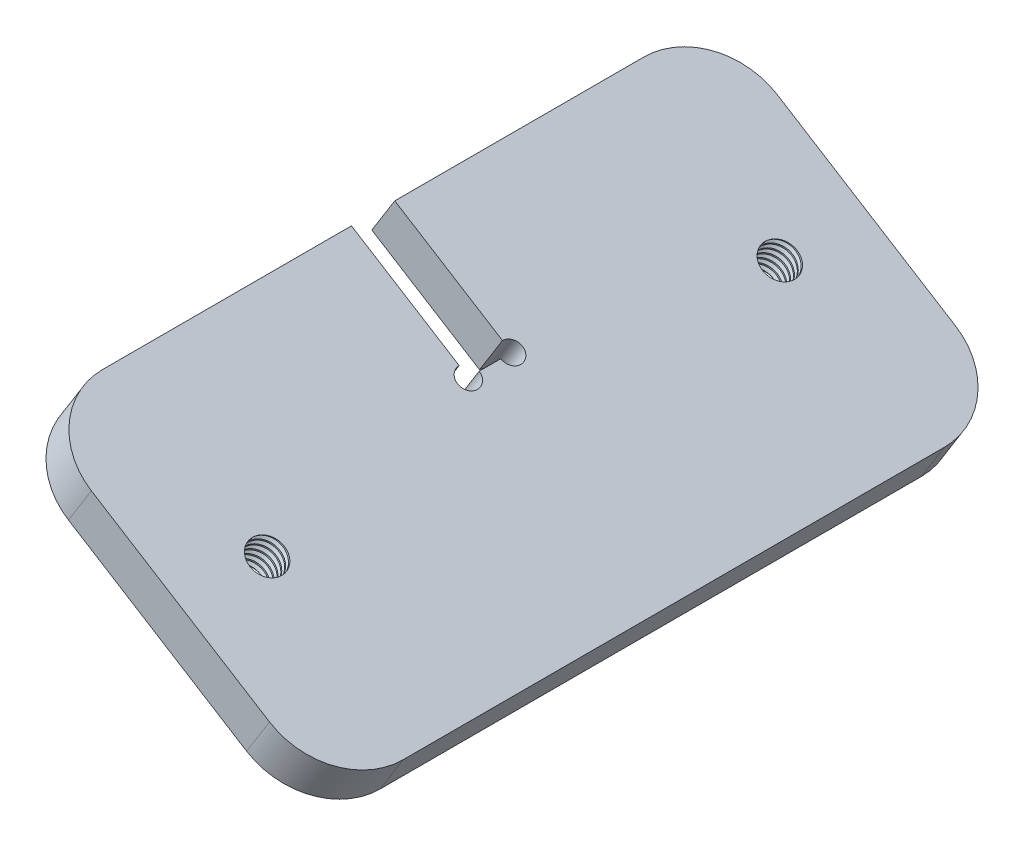
SolidWorks part; units mm, degrees
material "Plain Carbon Steel"
ref_plane "Front Plane" through (0, 0, 0) normal (0, 0, 1) x (1, 0, 0)
ref_plane "Top Plane" through (0, 0, 0) normal (0, 1, 0) x (1, 0, 0)
ref_plane "Right Plane" through (0, 0, 0) normal (1, 0, 0) x (0, 0, -1)
sketch "Sketch1" plane through (0, 0, 0) normal (0, 0, 1) x (1, 0, 0)
  line L0 (711, 132.9292) -> (685.5433, 148.8023)
  line L1 (685.5433, 148.8023) -> (688.7179, 153.8936)
  line L2 (711, 132.9292) -> (714.1746, 138.0205)
  line L3 (714.1746, 138.0205) -> (688.7179, 153.8936)
  line L4 (686.337, 150.0751) -> (688.7179, 153.8936) construction
  line L5 (688.7179, 153.8936) -> (672.5291, 163.9879) construction
  line L8 (711, 132.9292) -> (686.8161, 148.0087) construction
  line L9 (711, 132.9292) -> (711, 120) construction
extrude "Boss-Extrude1" add sketch "Sketch1" along normal up to surface (47.5 mm away) and the other way up to surface (47.5 mm away)
sketch "Sketch2" plane through (261.9022, 420.0282, 0) normal (0.5291, 0.8486, 0) x (0.8486, -0.5291, 0)
  line L0 (502.9903, 47.5) -> (483.9122, 47.5)
  line L1 (483.9122, 47.5) -> (483.9122, 3)
  line L2 (483.9122, -47.5) -> (502.9903, -47.5)
  line L3 (502.9903, -47.5) -> (502.9903, -3)
  line L5 (483.9122, 3) -> (483.9122, -3) construction
  line L6 (483.9122, 3) -> (502.9903, 3)
  line L7 (483.9122, 3) -> (502.9903, 3) construction
  line L8 (483.9122, -3) -> (502.9903, -3)
  line L9 (502.9903, -3) -> (483.9122, -3) construction
  line L10 (483.9122, -3) -> (483.9122, -47.5)
  line L11 (502.9903, 3) -> (502.9903, 47.5)
extrude "Boss-Extrude2" add sketch "Sketch2" against normal up to vertex (6 mm away)
fillet "Fillet1" radius 10 4 edges at (712.5873, 135.4748, -47.5) (670.9418, 161.4423, -47.5) (670.9418, 161.4423, 47.5) (712.5873, 135.4748, 47.5)
sketch "Sketch3" plane through (261.9022, 420.0282, 0) normal (0.5291, 0.8486, 0) x (0.8486, -0.5291, 0)
  line L0 (508.4512, -47.5) -> (508.4512, 47.5) construction
  line L1 (493.9122, -47.5) -> (522.9903, -47.5) construction
  line L2 (493.9122, 47.5) -> (522.9903, 47.5) construction
  line L3 (508.4512, 0) -> (532.9903, 0) construction
  line L4 (532.9903, -37.5) -> (532.9903, 37.5) construction
  circle A0 centre (502.9903, -3) radius 1.5
  circle A1 centre (502.9903, 3) radius 1.5
  circle A2 centre (508.4512, -35.5) radius 2.4
  circle A3 centre (508.4512, 35.5) radius 2.4
  dimension "D1" = 3
  dimension "D2" = 3
  dimension "D3" = 4.8
  dimension "D4" = 12
extrude "Cut-Extrude1" cut sketch "Sketch3" against normal through all
thread "Thread1" pitch 1 start angle 0, offset 0, length 10, pitch 1, diameter 4.8
ref_plane "Plane1" through (691.3153, 152.2741, 35.5) normal (0, 0, 1) x (-0.8486, 0.5291, 0)
sketch "Thread Profile1" plane through (691.3153, 152.2741, 35.5) normal (0, 0, 1) x (-0.8486, 0.5291, 0)
  line L0 (0, 0) -> (0, 1) construction
  line L1 (0, 0) -> (0.5413, 0.3125)
  line L2 (0.5413, 0.3125) -> (0.5413, 0.4375)
  line L3 (0.5413, 0.4375) -> (0, 0.75)
  line L4 (0.5413, 0.375) -> (0, 0.375) construction
  line L11 (0, 0) -> (0, 0.75)
  point P2 (0, 0)
  dimension "Pitch" = 1
  dimension "Profile_Angle" = 60
  dimension "Profile_Land" = 0.125
  dimension "Profile_Height" = 0.5413
thread "Thread2" pitch 1 profile "Thread Profile2" start angle 0, offset 0, length 10, pitch 1, diameter 4.8
ref_plane "Plane2" through (691.3153, 152.2741, -35.5) normal (0, 0, 1) x (-0.8486, 0.5291, 0)
sketch "Thread Profile2" plane through (691.3153, 152.2741, -35.5) normal (0, 0, 1) x (-0.8486, 0.5291, 0)
  line L0 (0, 0) -> (0, 1) construction
  line L1 (0, 0) -> (0.5413, 0.3125)
  line L2 (0.5413, 0.3125) -> (0.5413, 0.4375)
  line L3 (0.5413, 0.4375) -> (0, 0.75)
  line L4 (0.5413, 0.375) -> (0, 0.375) construction
  line L11 (0, 0) -> (0, 0.75)
  point P2 (0, 0)
  dimension "Pitch" = 1
  dimension "Profile_Angle" = 60
  dimension "Profile_Land" = 0.125
  dimension "Profile_Height" = 0.5413
